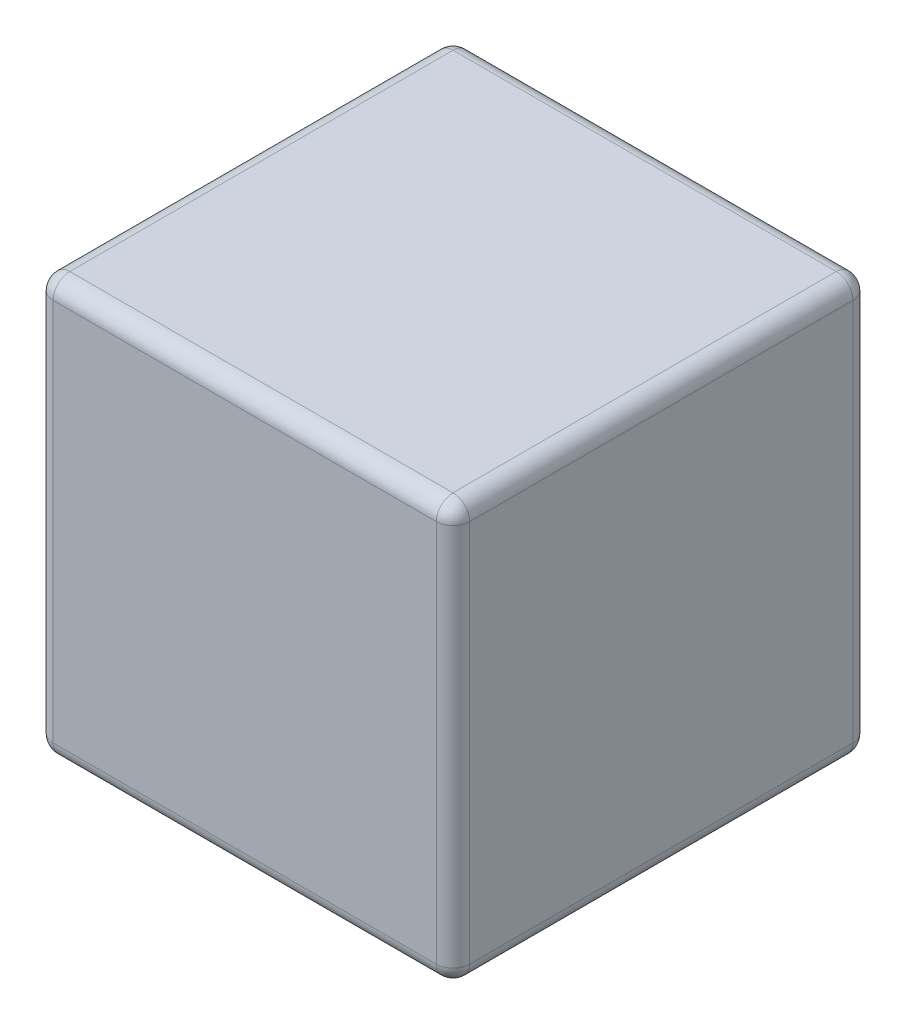
SolidWorks part; units mm, degrees
ref_plane "Front Plane" through (0, 0, 0) normal (0, 0, 1) x (1, 0, 0)
ref_plane "Top Plane" through (0, 0, 0) normal (0, 1, 0) x (1, 0, 0)
ref_plane "Right Plane" through (0, 0, 0) normal (1, 0, 0) x (0, 0, -1)
sketch "Sketch1" plane through (0, 0, 0) normal (0, 1, 0) x (1, 0, 0)
  line L1 (-125, -125) -> (125, -125)
  line L2 (-125, -125) -> (-125, 125)
  line L3 (-125, 125) -> (125, 125)
  line L4 (125, -125) -> (125, 125)
  line L5 (-125, -125) -> (125, 125) construction
  line L6 (-125, 125) -> (125, -125) construction
  point P0 (0, 0)
  dimension "D1" = 250
  dimension "D2" = 250
extrude "Boss-Extrude1" add sketch "Sketch1" along normal mid plane 250
fillet "Fillet1" radius 10 12 edges at (-125, 0, -125) (0, -125, -125) (-125, -125, 0) (125, 0, -125) (125, -125, 0) (-125, 0, 125) (125, 0, 125) (0, -125, 125) (0, 125, 125) (-125, 125, 0) (0, 125, -125) (125, 125, 0)
sketch "Sketch2" plane through (0, 0, -125) normal (0, 0, -1) x (-1, 0, 0)
  text T0 "LIFE SUPPORT" font "Century Gothic" height 25
extrude "Cut-Extrude1" cut sketch "Sketch2" against normal blind 5
